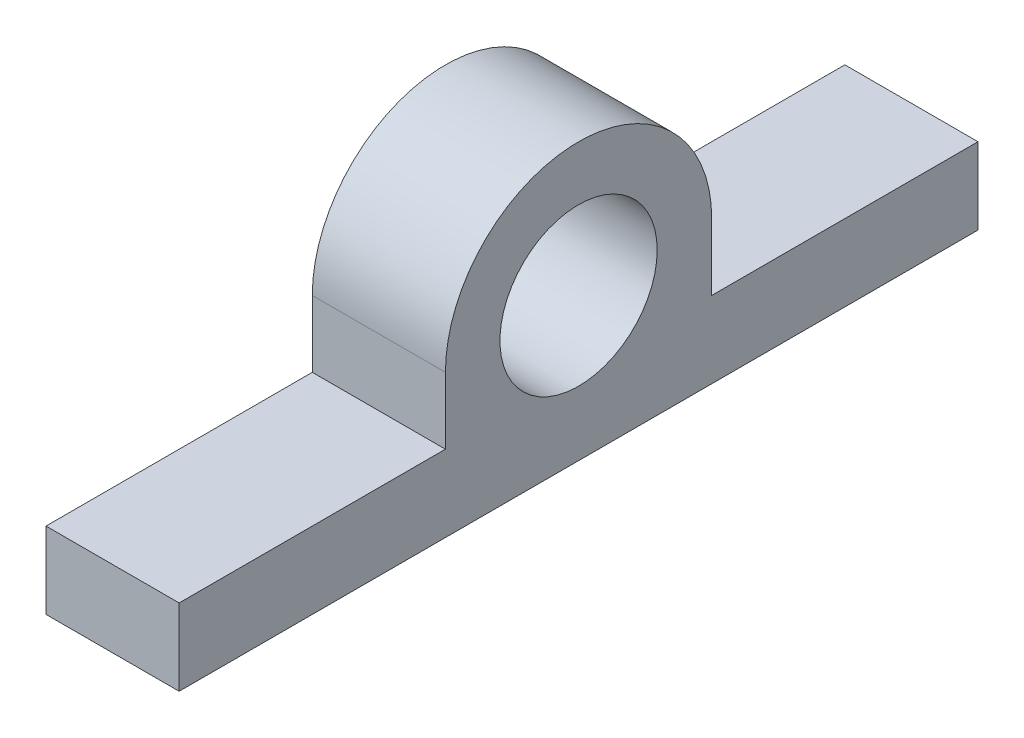
SolidWorks part; units mm, degrees
ref_plane "Front Plane" through (0, 0, 0) normal (0, 0, 1) x (1, 0, 0)
ref_plane "Top Plane" through (0, 0, 0) normal (0, 1, 0) x (1, 0, 0)
ref_plane "Right Plane" through (0, 0, 0) normal (1, 0, 0) x (0, 0, -1)
sketch "Sketch1" plane through (0, 0, 0) normal (1, 0, 0) x (0, 0, -1)
  line L0 (0, 0) -> (76.2, 0)
  line L1 (76.2, 0) -> (76.2, 7.3)
  line L2 (76.2, 7.3) -> (50.8, 7.3)
  line L3 (0, 7.3) -> (0, 0)
  line L5 (50.8, 7.3) -> (50.8, 13.65)
  line L7 (25.4, 13.65) -> (25.4, 7.3)
  line L9 (25.4, 7.3) -> (0, 7.3)
  arc A0 (50.8, 13.65) -> (25.4, 13.65) centre (38.1, 13.65) ccw
  dimension "D1" = 76.2
  dimension "D2" = 7.3
  dimension "D3" = 25.4
  dimension "D4" = 25.4
  dimension "D5" = 6.35
extrude "Boss-Extrude1" add sketch "Sketch1" along normal blind 12.7
sketch "Sketch2" plane through (12.7, 0, 0) normal (1, 0, 0) x (0, 0, -1)
  circle A0 centre (38.1, 13.65) radius 7.5
  dimension "D1" = 15
extrude "Cut-Extrude1" cut sketch "Sketch2" against normal through all
sketch "Sketch3" plane through (0, 0, 0) normal (0, -1, 0) x (1, 0, 0)
  line L0 (12.7, -76.2) -> (0, -76.2) construction
  line L3 (12.7, 0) -> (0, 0) construction
  circle A0 centre (6.35, -12.7) radius 2
  circle A1 centre (6.35, -63.5) radius 2
  point P4 (6.35, 0)
  point P10 (6.35, -76.2)
  dimension "D1" = 4
  dimension "D4" = 4
  dimension "D6" = 12.7
  dimension "D2" = 0
  dimension "D3" = 12.7
  dimension "D5" = 0
  dimension "D7" = 50.8
extrude "Cut-Extrude2" cut sketch "Sketch3" against normal blind 7
equation "\"bearing_d\"= 0.5in"
equation "\"heat_set_d\"= 0.1in"
